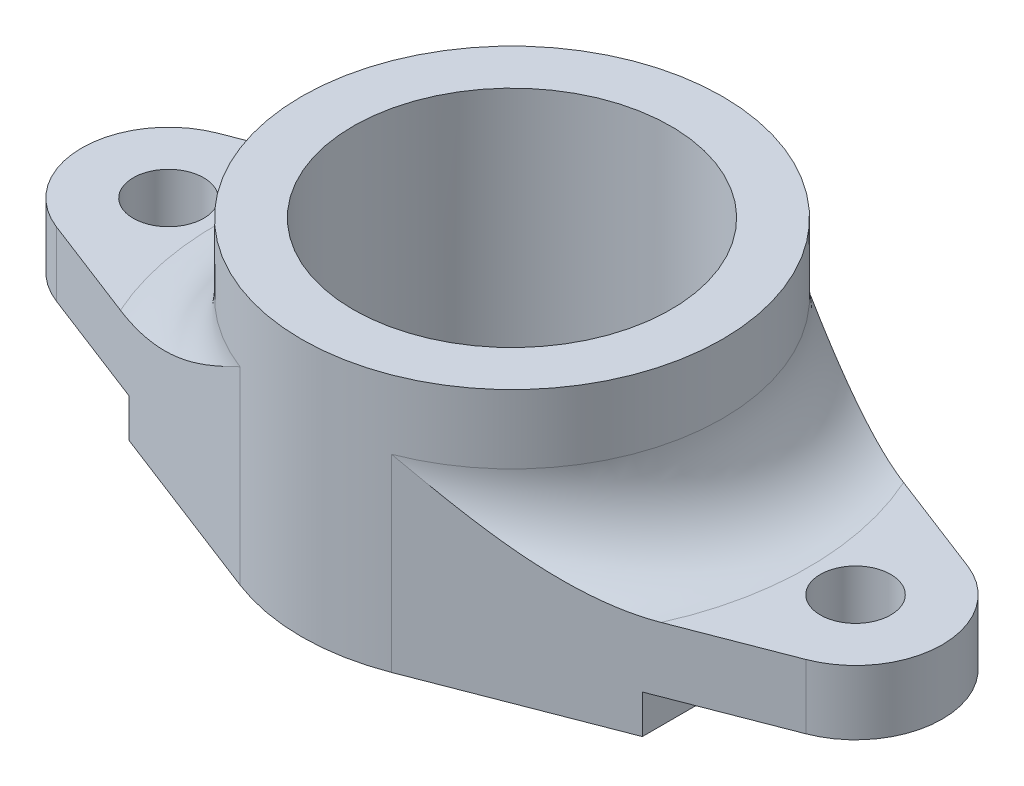
SolidWorks part; units mm, degrees
material "PE High Density"
ref_plane "Front Plane" through (0, 0, 0) normal (0, 0, 1) x (1, 0, 0)
ref_plane "Top Plane" through (0, 0, 0) normal (0, 1, 0) x (1, 0, 0)
ref_plane "Right Plane" through (0, 0, 0) normal (1, 0, 0) x (0, 0, -1)
sketch "Sketch1" plane through (0, 0, 0) normal (0, 1, 0) x (1, 0, 0)
  line L0 (-40, 0) -> (40, 0) construction
  line L1 (-43.636, 9.4228) -> (-8.82, 22.8573)
  line L2 (43.636, 9.4228) -> (8.82, 22.8573)
  line L3 (0, 0) -> (0, 24.5) construction
  line L4 (43.636, -9.4228) -> (8.82, -22.8573)
  line L5 (-43.636, -9.4228) -> (-8.82, -22.8573)
  line L6 (-41.476, 3.8251) -> (-43.636, 9.4228) construction
  line L7 (0, 18.5) -> (0, 24.5) construction
  line L8 (0, -24.5) -> (0, -18.5) construction
  circle A0 centre (0, 0) radius 18.5
  circle A1 centre (-40, 0) radius 4.1
  circle A2 centre (40, 0) radius 4.1
  arc A3 (-43.636, 9.4228) -> (-43.636, -9.4228) centre (-40, 0) ccw
  arc A4 (43.636, -9.4228) -> (43.636, 9.4228) centre (40, 0) ccw
  arc A5 (-8.82, -22.8573) -> (8.82, -22.8573) centre (0, 0) ccw
  arc A6 (8.82, 22.8573) -> (-8.82, 22.8573) centre (0, 0) ccw
  dimension "D1" = 37
  dimension "D2" = 8.2
  dimension "D3" = 80
  dimension "D4" = 6
extrude "Boss-Extrude1" add sketch "Sketch1" along normal blind 30
sketch "Sketch2" plane through (0, 30, 0) normal (0, 1, 0) x (1, 0, 0)
  circle A0 centre (0, 0) radius 24.5
  arc A1 (-8.82, -22.8573) -> (8.82, -22.8573) centre (0, 0) ccw construction
extrude "Cut-Extrude1" cut sketch "Sketch2" against normal offset from surface (18 mm away) 12 flip side to cut up to face at (0, 0, 0)
sketch "Sketch3" plane through (0, 0, 0) normal (1, 0, 0) x (0, 0, -1)
  line L0 (32.7798, 18.6737) -> (24.1434, -14.4349)
  line L1 (24.1434, -14.4349) -> (5, 0)
  line L2 (-9.4228, 0) -> (9.4228, 0) construction
  arc A0 (5, 0) -> (32.7798, 18.6737) centre (5, 30) ccw
  dimension "D1" = 30
  dimension "D2" = 5
extrude "Cut-Extrude2" cut sketch "Sketch3" against normal through all and the other way through all
fillet "Fillet1" radius 10 2 edges at (24.5, 12, 0) (-24.5, 12, 0)
sketch "Sketch4" plane through (0, 0, 0) normal (0, -1, 0) x (1, 0, 0)
  line L0 (-50.1, 20.6944) -> (-50.1, -20.6944)
  line L1 (-50.1, 20.6944) -> (-29.9, 20.6944)
  line L2 (-50.1, -20.6944) -> (-29.9, -20.6944)
  line L3 (-29.9, 20.6944) -> (-29.9, -20.6944)
  line L4 (-50.1, 20.6944) -> (-29.9, -20.6944) construction
  line L5 (-50.1, -20.6944) -> (-29.9, 20.6944) construction
  line L6 (29.9, 16.6796) -> (29.9, -16.6796)
  line L7 (29.9, 16.6796) -> (50.1, 16.6796)
  line L8 (29.9, -16.6796) -> (50.1, -16.6796)
  line L9 (50.1, 16.6796) -> (50.1, -16.6796)
  line L10 (29.9, 16.6796) -> (50.1, -16.6796) construction
  line L11 (29.9, -16.6796) -> (50.1, 16.6796) construction
  arc A0 (48.7755, -5) -> (43.636, 9.4228) centre (40, 0) ccw construction
  circle A1 centre (40, 0) radius 4.1 construction
  circle A2 centre (-40, 0) radius 4.1 construction
  arc A3 (-43.636, 9.4228) -> (-48.7755, -5) centre (-40, 0) ccw construction
  point P1 (-40, 0)
  point P2 (40, 0)
extrude "Cut-Extrude3" cut sketch "Sketch4" against normal blind 4.5
